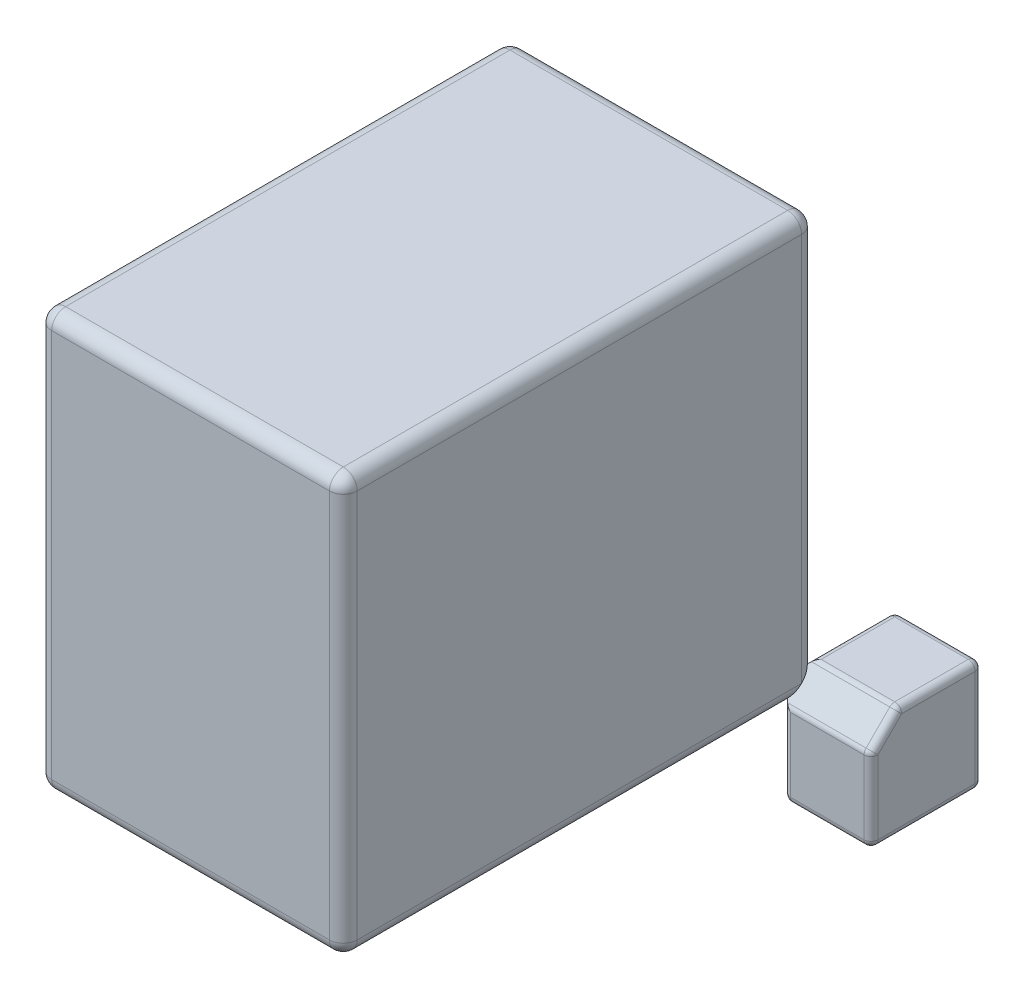
SolidWorks part; units mm, degrees
ref_plane "Front Plane" through (0, 0, 0) normal (0, 0, 1) x (1, 0, 0)
ref_plane "Top Plane" through (0, 0, 0) normal (0, 1, 0) x (1, 0, 0)
ref_plane "Right Plane" through (0, 0, 0) normal (1, 0, 0) x (0, 0, -1)
sketch "Sketch1" plane through (0, 0, 0) normal (0, 0, 1) x (1, 0, 0)
  line L1 (0, 0) -> (22, 0)
  line L2 (0, 0) -> (0, 30)
  line L3 (0, 30) -> (22, 30)
  line L4 (22, 0) -> (22, 30)
  dimension "D1" = 22
  dimension "D2" = 30
extrude "Boss-Extrude1" add sketch "Sketch1" along normal blind 34
sketch "Sketch2" plane through (0, 0, 0) normal (0, 0, -1) x (-1, 0, 0)
  line L0 (-22, 0) -> (-22, 30) construction
  line L1 (-20, 2) -> (-28, 2)
  line L2 (-20, 2) -> (-20, -6)
  line L3 (-20, -6) -> (-28, -6)
  line L4 (-28, 2) -> (-28, -6)
  line L5 (0, 0) -> (-22, 0) construction
  dimension "D1" = 2
  dimension "D2" = 2
  dimension "D3" = 8
  dimension "D4" = 8
shell "Shell1" thickness 1
extrude "Boss-Extrude3" add sketch "Sketch2" along normal blind 6 and the other way blind 2 contours L3 L4 L1 L2
chamfer "Chamfer2" distance 2 angle 45 3 edges at (25, 2, 2) (20, 2, -3) (20, -3, 2)
fillet "Fillet1" radius 1 12 edges at (0, 15, 0) (10, 0, 0) (22, 16, 0) (11, 30, 0) (11, 0, 34) (22, 15, 34) (11, 30, 34) (0, 30, 17) (22, 30, 17) (22, 0, 18) (0, 0, 17) (0, 15, 34)
fillet "Fillet2" radius 0.5 18 edges at (28, -6, -2) (24, -6, -6) (21, -6, 1) (25, -6, 2) (20, -6, -3) (20, -3, -6) (20, 0, -3) (20, -3, 0) (25, 0, 2) (21, 1, -6) (25, 2, -6) (28, 2, -3) (25, 2, 0) (22, 2, -3) (28, -3, 2) (28, -2, -6) (22, -3, 2) (28, 1, 1)
